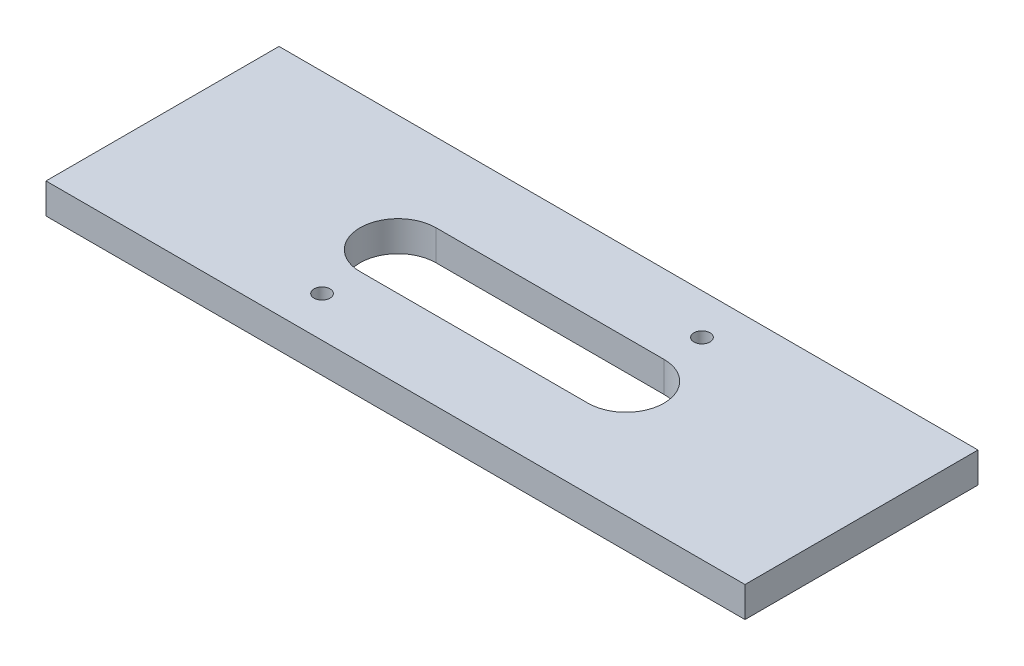
SolidWorks part; units mm, degrees
material "Pine"
ref_plane "Front Plane" through (0, 0, 0) normal (0, 0, 1) x (1, 0, 0)
ref_plane "Top Plane" through (0, 0, 0) normal (0, 1, 0) x (1, 0, 0)
ref_plane "Right Plane" through (0, 0, 0) normal (1, 0, 0) x (0, 0, -1)
sketch "Sketch2" plane through (0, 0, 0) normal (0, 1, 0) x (1, 0, 0)
  line L4 (93, 46) -> (183, 46) construction
  line L5 (0, 0) -> (276, 0)
  line L6 (0, 0) -> (0, 92)
  line L7 (0, 92) -> (276, 92)
  line L8 (276, 0) -> (276, 92)
  line L9 (93, 61) -> (183, 61)
  line L10 (93, 31) -> (183, 31)
  arc A0 (93, 61) -> (93, 31) centre (93, 46) ccw
  arc A1 (183, 31) -> (183, 61) centre (183, 46) ccw
  point P7 (138, 46)
  point P12 (138, 0)
  point P13 (0, 46)
  dimension "D5" = 15
  dimension "full_width" = 276
  dimension "D3" = 46
  dimension "D6" = 90
  dimension "D4" = 93
  dimension "D1" = 92
extrude "Boss-Extrude1" add sketch "Sketch2" along normal blind 12 contours L7 L8 L5 L6
extrude "Cut-Extrude1" cut sketch "Sketch2<3>" along normal up to surface (12 mm away) contours A0 L10 A1 L9 up to face at (138, 12, -46)
sketch "Sketch2<3>" plane through (0, 0, 0) normal (0, 1, 0) x (1, 0, 0) same geometry as "Sketch2"
sketch "Sketch3" plane through (70, 12, 0) normal (0, 1, 0) x (1, 0, 0)
  circle A0 centre (113, 76) radius 3.175
  circle A1 centre (23, 16) radius 3.175
extrude "Cut-Extrude2" cut sketch "Sketch3" against normal up to surface (12 mm away) up to face at (138, 0, -46)
equation "\"LENGTH\" = 1000mm"
equation "\"PLY\"= 12mm"
equation "\"D1@Boss-Extrude1\"=\"PLY\""
equation "\"WIDTH\" = 300mm"
equation "\"HEIGHT\" = 300mm"
equation "\"HOUSING_DEPTH\" = 4mm"
equation "\"CENTER_BRACE_LENGTH\" = 393mm"
equation "\"PANEL_WIDTH\"= \"LENGTH\" - \"CENTER_BRACE_LENGTH\" * 2 - \"PLY\" * 4"
equation "\"PANEL_SMALL_HEIGHT\" = 70mm"
equation "\"PORT_WIDTH\" = 90mm"
equation "\"PORT_RADIUS\" = 15mm"
equation "\"full_width@Sketch2\" = \"WIDTH\" - \"PLY\" * 2"
equation "\"PORT_BRACE_HEIGHT\" = 92mm"
equation "\"D6@Sketch2\"=\"PORT_WIDTH\""
equation "\"D5@Sketch2\"=\"PORT_RADIUS\""
equation "\"D4@Sketch2\"=\"full_width@Sketch2\" / 2 - \"PORT_WIDTH\" / 2"
equation "\"D1@Sketch2\"=\"PORT_BRACE_HEIGHT\""
